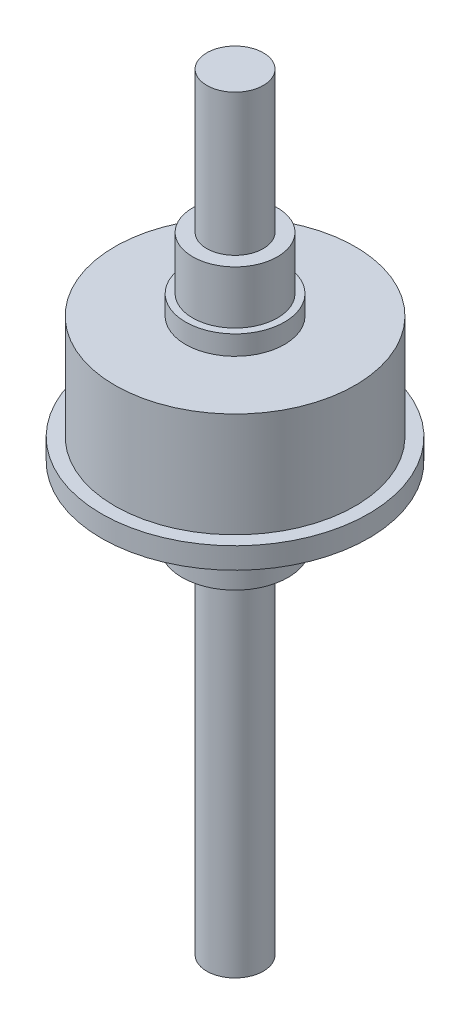
SolidWorks part; units mm, degrees
material "AISI 1035 Steel (SS)"
ref_plane "Front Plane" through (0, 0, 0) normal (0, 0, 1) x (1, 0, 0)
ref_plane "Top Plane" through (0, 0, 0) normal (0, 1, 0) x (1, 0, 0)
ref_plane "Right Plane" through (0, 0, 0) normal (1, 0, 0) x (0, 0, -1)
sketch "Sketch2" plane through (0, 0, 0) normal (0, 0, 1) x (1, 0, 0)
  line L0 (0, 40.0334) -> (0, -27.2464) construction
  line L11 (0, 0) -> (-4, 0)
  line L12 (-4, 0) -> (-4, -20)
  line L13 (-4, -20) -> (-6, -20)
  line L14 (-6, -20) -> (-6, -27.5)
  line L15 (-6, -27.5) -> (-7, -27.5)
  line L16 (-7, -27.5) -> (-7, -30.25)
  line L17 (-7, -30.25) -> (-17, -30.25)
  line L18 (-17, -30.25) -> (-17, -45.05)
  line L26 (0, -108.55) -> (0, 0)
  line L28 (-18.9, -48.05) -> (-18.9, -45.05)
  line L29 (-18.9, -45.05) -> (-17, -45.05)
  line L30 (-18.9, -48.05) -> (-10, -48.05)
  line L31 (-10, -48.05) -> (-10, -50.55)
  line L32 (-17, -45.05) -> (-17, -48.05) construction
  line L33 (-10, -50.55) -> (-7.5, -50.55)
  line L34 (-7.5, -50.55) -> (-7.5, -58.55)
  line L35 (-7.5, -58.55) -> (-4, -58.55)
  line L36 (-4, -58.55) -> (-4, -108.55)
  line L37 (-4, -108.55) -> (0, -108.55)
  dimension "D1" = 4
  dimension "D2" = 20
  dimension "D3" = 6
  dimension "D4" = 7.5
  dimension "D5" = 7
  dimension "D6" = 2.75
  dimension "D7" = 17
  dimension "D8" = 14.8
  dimension "D10" = 3
  dimension "D11" = 10
  dimension "D12" = 2.5
  dimension "D13" = 7.5
  dimension "D14" = 8
  dimension "D15" = 4
  dimension "D16" = 50
  dimension "D9" = 1.9
revolve "Revolve1" add sketch "Sketch2" angle 360 about L0
equation "\"Stator_OD\"= 68'No Tolerance given"
equation "\"A\"=18.34"
equation "\"Rotor_ID\"= 34'No Tolerance Given"
equation "\"back_bearing_Thickness\"= 8'randomish, thinnest off mcmaster"
equation "\"back_bearing_OD\"= 25'currently non-sense"
equation "\"Stator_Gap\"= 0.0375'+- 0.0125 (From 1.3.3.1 Kollmorgen manual)"
equation "\"Back_mount_hole\"= 1.75'To be tapped to M2 (USE LOCKTITE)"
equation "\"facePlate_Mount_Hole\"= 5.75'To be tapped to M6"
equation "\"final_shaftD\"= 8'NEMA 23 shaft diameter. Should fit with harmonic?"
equation "\"back_bearing_ID\"= 15'Random number"
equation "\"rotor_shaftD\"= \"Rotor_ID\" - (0.0185)*2'+-0.0065 (from manual)"
equation "\"back_bearing_IDOD\"= 20'Random number, OD of the inner bearing ring"
equation "\"final_shaftL\"= 50'random length. Idk"
equation "\"D1@Sketch2\" = \"final_shaftD\" / 2"
equation "\"D3@Sketch2\"=\"front_bearing_ID\"/2"
equation "\"D4@Sketch2\" = \"front_bearing_Thickness\" + 2.5"
equation "\"D5@Sketch2\"=\"front_bearing_IDOD\" / 2"
equation "\"D8@Sketch2\"=\"rotor_height\""
equation "\"front_bearing_ID\"= 12'random"
equation "\"front_bearing_OD\"= 20'random"
equation "\"front_bearing_IDOD\"= 14'random"
equation "\"front_bearing_Thickness\"= 5'randomish, thinnest off mcmaster"
equation "\"rotor_thickness\"= 2.4'measured off CAD"
equation "\"rotor_height\"= 14.8'measured off CAD"
equation "\"D11@Sketch2\"=\"back_bearing_IDOD\"/2"
equation "\"D13@Sketch2\"=\"back_bearing_ID\"/2"
equation "\"D14@Sketch2\"=\"back_bearing_Thickness\""
equation "\"D15@Sketch2\"=\"final_shaftD\"/2"
equation "\"D16@Sketch2\"=\"final_shaftL\""
equation "\"D9@Sketch2\"=\"rotor_thickness\"-0.5"
